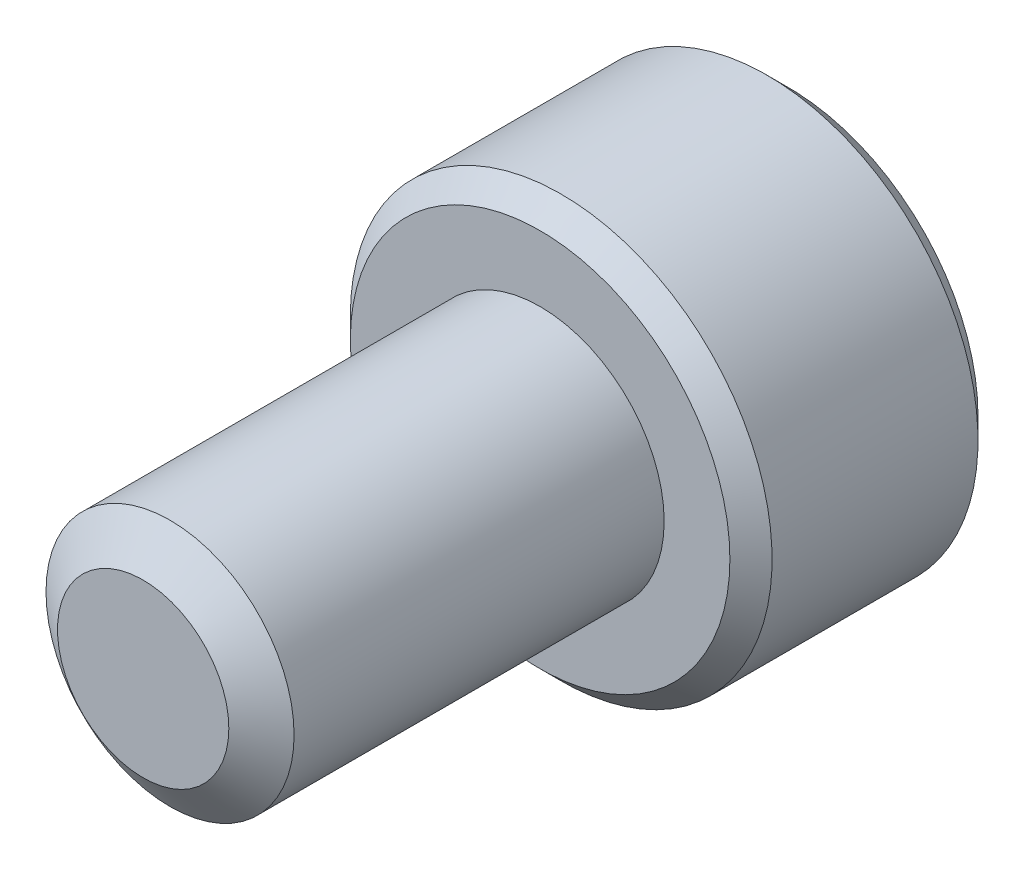
SolidWorks part; units mm, degrees
other "DetailItem1"
material "1.4310 (X10CrNi18-8)"
ref_plane "Front Plane" through (0, 0, 0) normal (0, 0, 1) x (1, 0, 0)
ref_plane "Top Plane" through (0, 0, 0) normal (0, 1, 0) x (1, 0, 0)
ref_plane "Right Plane" through (0, 0, 0) normal (1, 0, 0) x (0, 0, -1)
sketch "Sketch1" plane through (0, 0, 0) normal (0, 0, 1) x (1, 0, 0)
  circle A0 centre (0, 0) radius 2.5
  dimension "OD" = 5
extrude "Extrude1" add sketch "Sketch1" against normal blind 8
sketch "Sketch2" plane through (0, 0, 0) normal (0, 0, 1) x (1, 0, 0)
  circle A0 centre (0, 0) radius 2.5 construction
  circle A1 centre (0, 0) radius 2.5
curve "Helix/Spiral1" pitch 0.8 height 8.8 turns 11 parameters "pitch"=0.8
sketch "Sketch3" plane through (0, 0, 0) normal (1, 0, 0) x (0, 0, -1)
  line L0 (-0.7, 2.5) -> (-0.4, 1.9804)
  line L1 (-0.4, 1.9804) -> (-0.3, 1.9804)
  line L2 (-0.3, 1.9804) -> (0, 2.5)
  line L3 (-0.7, 2.5) -> (0, 2.5)
  line L4 (-0.35, 2.5) -> (-0.35, 1.9804) construction
  line L5 (-0.55, 2.2402) -> (-0.15, 2.2402) construction
  line L6 (0, 2.5) -> (0, -2.5) construction
  dimension "D1" = 0.1
  dimension "D2" = 0.4
  dimension "D3" = 60
sweep "Cut-Sweep1" [suppressed] cut profiles "Sketch3" path "Helix/Spiral1"
sketch "Sketch4" plane through (0, 0, 0) normal (1, 0, 0) x (0, 0, -1)
  line L0 (0.5417, 2.5) -> (0, 1.7264)
  line L1 (0, 1.7264) -> (0, 2.5)
  line L2 (0.5417, 2.5) -> (0, 2.5)
  line L3 (-0.7, 2.5) -> (0, 2.5) construction
  line L4 (0, 0) -> (7.0209, 0) construction
  dimension "D1" = 55
  dimension "D2" = 0.254
revolve "Cut-Revolve1" cut sketch "Sketch4" angle 360 about L4
sketch "Sketch6" plane through (0, 0, -8) normal (0, 0, -1) x (-1, 0, 0)
  circle A0 centre (0, 0) radius 4.25
  dimension "head dia" = 8.5
extrude "Extrude2" add sketch "Sketch6" along normal blind 5
sketch "Sketch7" plane through (0, 0, -13) normal (0, 0, -1) x (-1, 0, 0)
  line L1 (0, 2.3094) -> (-2, 1.1547)
  line L2 (-2, 1.1547) -> (-2, -1.1547)
  line L3 (-2, -1.1547) -> (0, -2.3094)
  line L4 (0, -2.3094) -> (2, -1.1547)
  line L5 (2, -1.1547) -> (2, 1.1547)
  line L6 (2, 1.1547) -> (0, 2.3094)
  circle A0 centre (0, 0) radius 2 construction
  dimension "hex dia" = 4
extrude "Cut-Extrude1" cut sketch "Sketch7" against normal blind 3
sketch "Sketch8" plane through (0, 0, -13) normal (0, 0, -1) x (-1, 0, 0)
  circle A0 centre (0, 0) radius 2.3094
extrude "Cut-Extrude2" cut sketch "Sketch8" against normal through all draft 45
chamfer "Chamfer1" distance 0.425 angle 45 2 edges at (-4.25, 0, -13) (-4.25, 0, -8)
sketch "Sketch10" plane through (0, 0, -8) normal (0, 0, 1) x (1, 0, 0)
  circle A1 centre (0, 0) radius 2.5
  circle A2 centre (0, 0) radius 2.5
  dimension "D1" = 0
ref_plane "Plane1" through (0, 0, 0) normal (0, 0, 1) x (1, 0, 0)
extrude "partial thread" [suppressed] add sketch "Sketch10" along normal up to surface (13 mm away) separate body up to plane "Plane1"
chamfer "Chamfer2" [suppressed] distance 0.1 angle 45
combine bodies "Combine1" [suppressed] operation type add bodies to combine 107 108
sketch "Sketch9" plane through (0, 0, 0) normal (1, 0, 0) x (0, 0, -1)
  line L0 (0, 2.5) -> (0, -2.5) construction
  line L1 (2, 2.5) -> (2, -2.5) construction
  dimension "D1" = 2
equation "\"D3@Helix/Spiral1\" = \"screw length@Extrude1\"+\"pitch@Helix/Spiral1\""
equation "\"D1@Sketch3\" = \"pitch@Helix/Spiral1\"*.125"
equation "\"D2@Sketch3\" = \"pitch@Helix/Spiral1\"*.5"
equation "\"D1@Cut-Extrude1\" = \"hex dia@Sketch7\"*.75"
equation "\"D1@Chamfer1\" = \"head dia@Sketch6\"*.05"
equation "\"D1@Sketch9\" = \"pitch@Helix/Spiral1\"*2.5"
equation "\"D1@Chamfer2\"=\"OD@Sketch1\"*.02"
